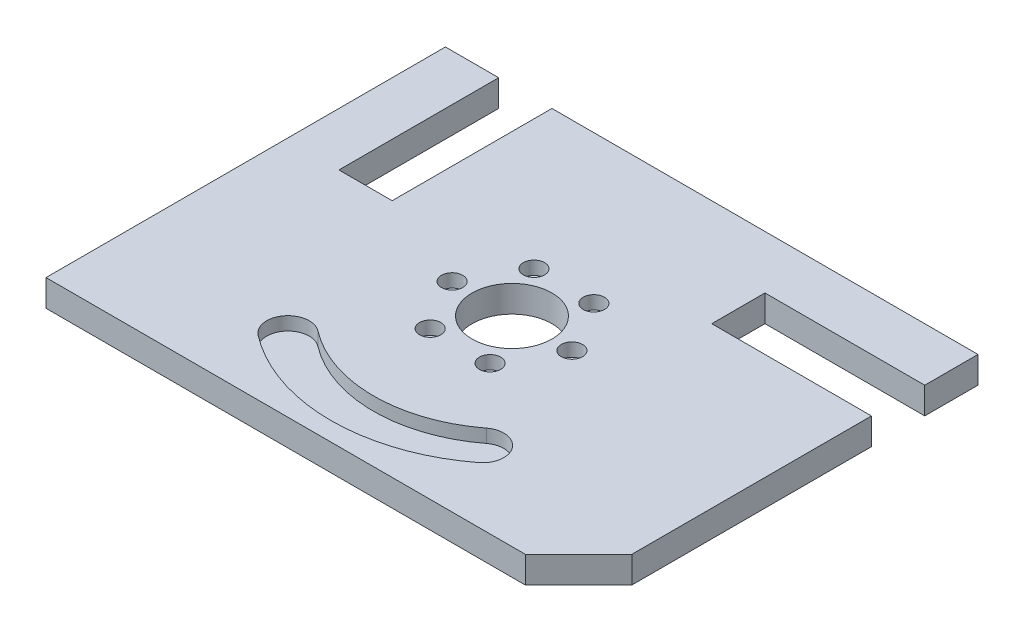
SolidWorks part; units mm, degrees
ref_plane "Front Plane" through (0, 0, 0) normal (0, 0, 1) x (1, 0, 0)
ref_plane "Top Plane" through (0, 0, 0) normal (0, 1, 0) x (1, 0, 0)
ref_plane "Right Plane" through (0, 0, 0) normal (1, 0, 0) x (0, 0, -1)
sketch "Sketch1" plane through (0, 0, 0) normal (0, 1, 0) x (1, 0, 0)
  line L0 (-80, 75) -> (-80, 15)
  line L1 (-100, 75) -> (-80, 75)
  line L2 (-100, 75) -> (-100, -75)
  line L3 (-100, -75) -> (100, -75)
  line L4 (100, 75) -> (100, 55)
  line L5 (-100, 75) -> (100, -75) construction
  line L6 (-100, -75) -> (100, 75) construction
  line L7 (-80, 15) -> (-60, 15)
  line L8 (-60, 15) -> (-60, 75)
  line L9 (100, 55) -> (40, 55)
  line L10 (40, 55) -> (40, 35)
  line L11 (40, 35) -> (100, 35)
  line L12 (-60, 75) -> (100, 75)
  line L13 (100, 35) -> (100, -75)
  point P0 (0, 0)
  dimension "D1" = 200
  dimension "D2" = 150
  dimension "D3" = 60
  dimension "D4" = 20
  dimension "D5" = 20
  dimension "D6" = 60
  dimension "D7" = 20
  dimension "D8" = 20
extrude "Boss-Extrude1" add sketch "Sketch1" along normal blind 10
sketch "Sketch2" plane through (0, 10, 0) normal (0, 1, 0) x (1, 0, 0)
  line L0 (0, -41.4408) -> (0, -78.5592) construction
  circle A0 centre (0, 0) radius 15
  circle A1 centre (0, 0) radius 22.5 construction
  circle A2 centre (22.5, 0) radius 4
  circle A3 centre (11.25, -19.4856) radius 4
  circle A4 centre (-11.25, -19.4856) radius 4
  circle A5 centre (-22.5, 0) radius 4
  circle A6 centre (-11.25, 19.4856) radius 4
  circle A7 centre (11.25, 19.4856) radius 4
  arc A8 (36.5213, -47.6046) -> (-36.5213, -47.6046) centre (0, 0) cw construction
  arc A9 (-41.3908, -53.9519) -> (41.3908, -53.9519) centre (0, 0) ccw
  arc A10 (-31.6518, -41.2573) -> (31.6518, -41.2573) centre (0, 0) ccw
  arc A11 (-31.6518, -41.2573) -> (-41.3908, -53.9519) centre (-36.5213, -47.6046) ccw
  arc A12 (41.3908, -53.9519) -> (31.6518, -41.2573) centre (36.5213, -47.6046) ccw
  point P18 (0, 0)
  point P19 (0, -60)
  dimension "D1" = 30
  dimension "D2" = 45
  dimension "D3" = 8
  dimension "D5" = 60
  dimension "D6" = 8
  dimension "D4" = 6
extrude "Cut-Extrude1" cut sketch "Sketch2" against normal through all contours A0
extrude "Cut-Extrude2" cut sketch "Sketch2<3>" against normal blind 5
sketch "Sketch2<3>" plane through (0, 10, 0) normal (0, 1, 0) x (1, 0, 0) same geometry as "Sketch2"
chamfer "Chamfer1" distance 20 angle 45 1 edges at (100, 5, 75)
